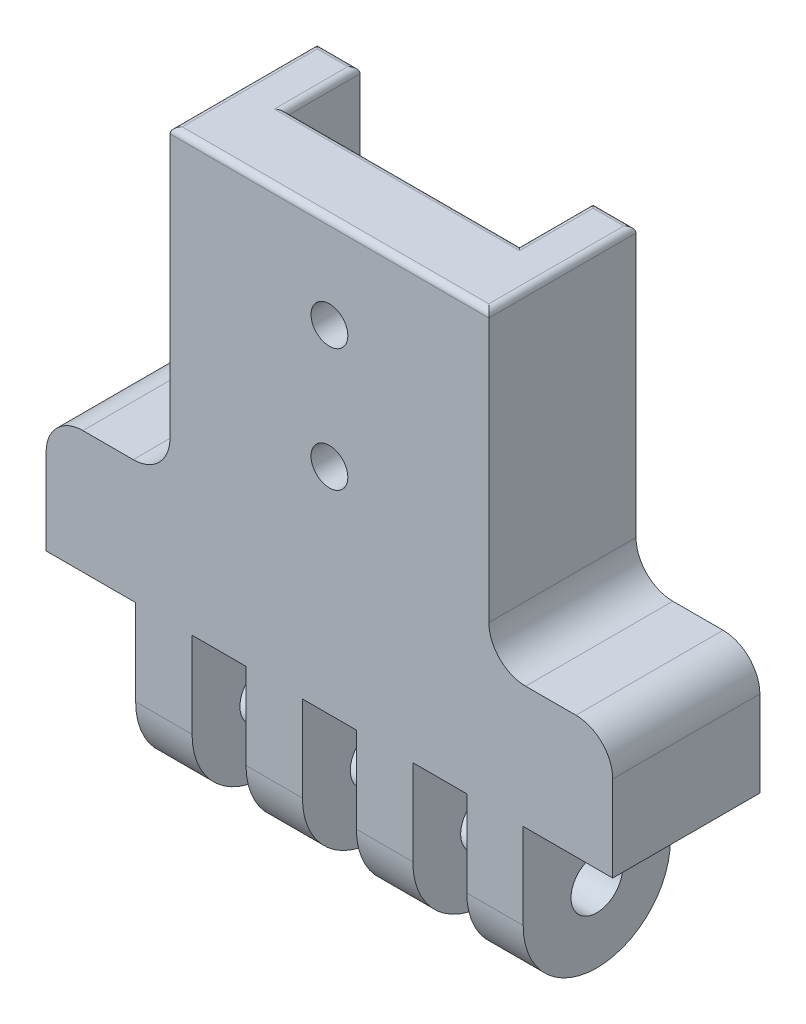
SolidWorks part; units mm, degrees
other "Markup1"
sketch "Sketch9" plane through (-23.1, -13, 8) normal (-0.4776, -0.6311, 0.6112) x (-0.7397, -0.0865, -0.6673)
ref_plane "Front Plane" through (0, 0, 0) normal (0, 0, 1) x (1, 0, 0)
ref_plane "Top Plane" through (0, 0, 0) normal (0, 1, 0) x (1, 0, 0)
ref_plane "Right Plane" through (0, 0, 0) normal (1, 0, 0) x (0, 0, -1)
sketch "Sketch1" plane through (0, 0, 0) normal (0, 1, 0) x (1, 0, 0)
  line L1 (23.1, 6) -> (-23.1, 6)
  line L2 (23.1, 6) -> (23.1, -6)
  line L3 (23.1, -6) -> (-23.1, -6)
  line L4 (-23.1, 6) -> (-23.1, -6)
  line L5 (23.1, 6) -> (-23.1, -6) construction
  line L6 (23.1, -6) -> (-23.1, 6) construction
  point P0 (0, 0)
  dimension "D1" = 12
  dimension "D2" = 46.2
extrude "Boss-Extrude1" add sketch "Sketch1" along normal blind 10
sketch "Sketch2" plane through (0, 0, 0) normal (0, -1, 0) x (1, 0, 0)
  line L0 (23.1, -6) -> (-23.1, -6) construction
  line L1 (15.8, -6) -> (11.2, -6)
  line L2 (15.8, -6) -> (15.8, 6)
  line L3 (15.8, 6) -> (11.2, 6)
  line L4 (11.2, -6) -> (11.2, 6)
  line L5 (13.5, 8) -> (13.5, -6) construction
  line L6 (15.8, 0) -> (11.2, 0) construction
  point P272 (13.5, 0)
  dimension "D1" = 12
  dimension "D2" = 4.6
extrude "Boss-Extrude2" add sketch "Sketch2" along normal blind 7
sketch "Sketch8" plane through (15.8, 0, 0) normal (1, 0, 0) x (0, 0, -1)
  line L0 (6, -7) -> (-6, -7) construction
  line L1 (6, -7) -> (6, 0) construction
  circle A0 centre (0, -7) radius 6
  dimension "D1" = 12
extrude "Boss-Extrude3" add sketch "Sketch8" against normal up to surface (4.6 mm away) up to face at (11.2, -3.5, 0)
pattern_linear "LPattern1" count 4 spacing 9 along (-1, 0, 0) of "Boss-Extrude2", "Boss-Extrude3"
sketch "Sketch4" plane through (15.8, 0, 0) normal (1, 0, 0) x (0, 0, -1)
  circle A0 centre (0, -7) radius 2.1
  arc A2 (-6, -7) -> (6, -7) centre (0, -7) ccw construction
  dimension "D1" = 4.2
  dimension "D2" = 0
extrude "Cut-Extrude1" cut sketch "Sketch4" against normal through all
ref_plane "Plane1" through (0, 10, 0) normal (0, 1, 0) x (1, 0, 0)
sketch "Sketch10" plane through (0, 10, 0) normal (0, 1, 0) x (1, 0, 0)
  line L0 (23.1, 6) -> (-23.1, 6) construction
  line L1 (13, -6) -> (-13, -6)
  line L2 (13, -6) -> (13, 6)
  line L3 (13, 6) -> (-13, 6)
  line L4 (-13, -6) -> (-13, 6)
  line L5 (13, -6) -> (-13, 6) construction
  line L6 (13, 6) -> (-13, -6) construction
  point P0 (0, 0)
  dimension "D1" = 26
extrude "Boss-Extrude4" add sketch "Sketch10" along normal blind 25
ref_plane "Plane2" through (0, 35, 0) normal (0, 1, 0) x (1, 0, 0)
sketch "Sketch11" plane through (0, 35, 0) normal (0, 1, 0) x (1, 0, 0)
  line L0 (13, 6) -> (-13, 6) construction
  line L1 (9.5, 0) -> (-9.5, 0)
  line L2 (9.5, 0) -> (9.5, 6)
  line L3 (9.5, 6) -> (-9.5, 6)
  line L4 (-9.5, 0) -> (-9.5, 6)
  line L5 (9.5, 0) -> (-9.5, 6) construction
  line L6 (9.5, 6) -> (-9.5, 0) construction
  line L7 (-13, 6) -> (-13, -6) construction
  point P0 (0, 3)
  point P7 (-9.5, 3)
  dimension "D1" = 19
  dimension "D2" = 6
  dimension "D3" = 13
extrude "Cut-Extrude2" cut sketch "Sketch11" against normal blind 25
fillet "Fillet1" radius 3 4 edges at (-13, 10, 0) (13, 10, 0) (23.1, 10, 0) (-23.1, 10, 0)
fillet "Fillet2" radius 0.5 8 edges at (-13, 35, 0) (-11.25, 35, -6) (-9.5, 35, -3) (0, 35, 0) (9.5, 35, -3) (11.25, 35, -6) (13, 35, 0) (0, 35, 6)
sketch "Sketch12" plane through (0, 0, 0) normal (0, 0, 1) x (1, 0, 0)
  line L0 (-18.4905, 22.5) -> (19.9775, 22.5) construction
  line L1 (-20.1, 10) -> (-16, 10) construction
  line L2 (13, 34.5) -> (13, 13) construction
  circle A0 centre (0, 17.5) radius 1.5
  circle A1 centre (0, 27.5) radius 1.5
  point P8 (0, 0)
  point P11 (0, 0)
  dimension "D1" = 3
  dimension "D2" = 10
  dimension "D3" = 5
  dimension "D4" = 12.5
  dimension "D5" = 13
extrude "Cut-Extrude3" cut sketch "Sketch12" against normal mid plane 20
